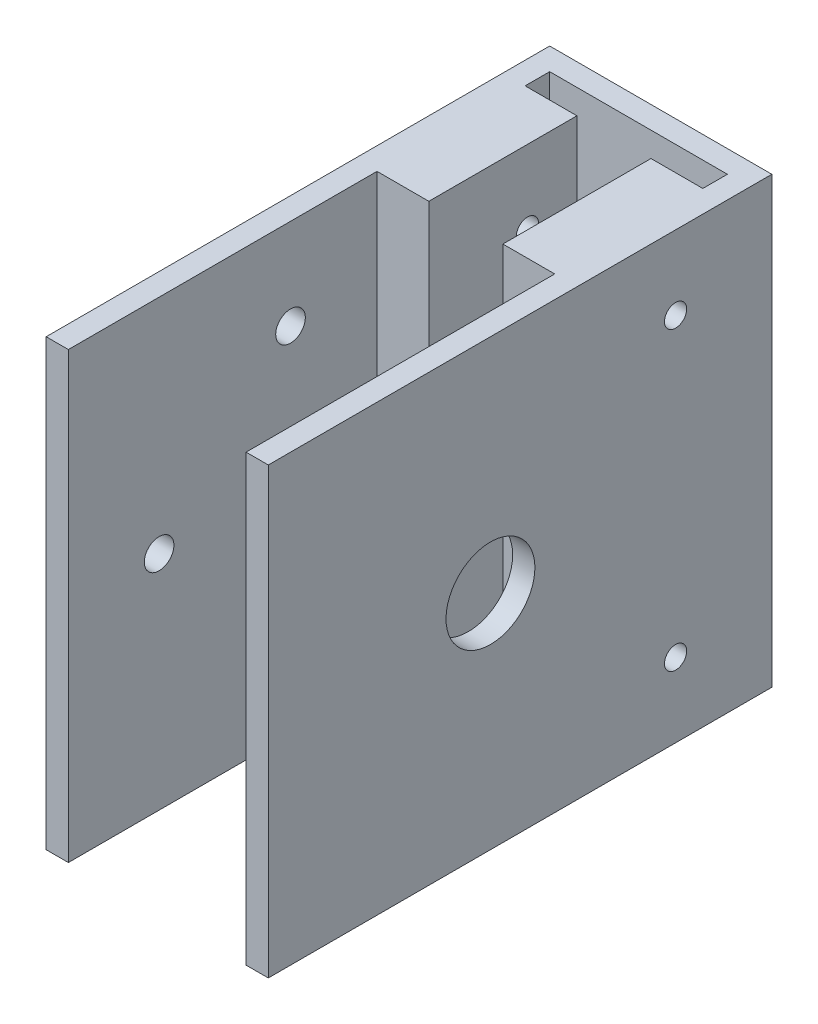
SolidWorks part; units mm, degrees
ref_plane "Front Plane" through (0, 0, 0) normal (0, 0, 1) x (1, 0, 0)
ref_plane "Top Plane" through (0, 0, 0) normal (0, 1, 0) x (1, 0, 0)
ref_plane "Right Plane" through (0, 0, 0) normal (1, 0, 0) x (0, 0, -1)
sketch "Sketch1" plane through (0, 0, 0) normal (0, 0, 1) x (1, 0, 0)
  line L0 (55, 0) -> (-55, 0) construction
  line L1 (-15, 30) -> (15, 30)
  line L2 (-15, 30) -> (-15, -30)
  line L3 (-15, -30) -> (15, -30)
  line L4 (15, 30) -> (15, -30)
  line L5 (-15, 30) -> (15, -30) construction
  line L6 (-15, -30) -> (15, 30) construction
  circle A0 centre (0, 15) radius 2.9
  circle A1 centre (0, -15) radius 2.9
  point P0 (0, 0)
  dimension "D3" = 15
  dimension "D4" = 5.8
  dimension "D1" = 30
  dimension "D2" = 60
extrude "Boss-Extrude1" add sketch "Sketch1" along normal blind 3
sketch "Sketch2" plane through (0, 0, 3) normal (0, 0, 1) x (1, 0, 0)
  line L0 (-15, -30) -> (15, -30) construction
  line L1 (-15, 30) -> (-12, 30)
  line L2 (-15, 30) -> (-15, -30)
  line L3 (-15, -30) -> (-12, -30)
  line L4 (-12, 30) -> (-12, -30)
  line L6 (15, 30) -> (12, 30)
  line L7 (15, 30) -> (15, -30)
  line L8 (15, -30) -> (12, -30)
  line L9 (12, 30) -> (12, -30)
  dimension "D1" = 3
  dimension "D2" = 3
extrude "Boss-Extrude2" add sketch "Sketch2" along normal blind 65
sketch "Sketch5" plane through (0, 30, 0) normal (0, 1, 0) x (1, 0, 0)
  line L0 (12, -68) -> (12, -3) construction
  line L2 (12, -6.3201) -> (5, -6.3201)
  line L3 (12, -6.3201) -> (12, -26.3201)
  line L4 (12, -26.3201) -> (5, -26.3201)
  line L5 (5, -6.3201) -> (5, -26.3201)
  line L6 (0, -33) -> (0, 33) construction
  line L7 (-12, -26.3201) -> (-5, -26.3201)
  line L8 (-12, -6.3201) -> (-5, -6.3201)
  line L9 (-5, -6.3201) -> (-5, -26.3201)
  line M5 (-12, -68) -> (-12, -3)
  line M7 (12, -3) -> (12, -68)
  dimension "D1" = 7
  dimension "D2" = 20
extrude "Boss-Extrude3" add sketch "Sketch5" against normal up to surface (60 mm away) contours L2 L5 L4 M7 | L9 L8 L7 M5 region at (8.5, 30, 16.3201) region at (-8.5, 30, 16.3201) up to face at (0, -30, 34.75)
sketch "Sketch3" plane through (-15, 0, 0) normal (-1, 0, 0) x (0, 0, 1)
  line L0 (68, 30) -> (0, 30) construction
  line L1 (0, 30) -> (0, -30) construction
  line L3 (16.5, 0) -> (-16.5, 0) construction
  circle A0 centre (13, 20) radius 1.5
  circle A1 centre (38, 0) radius 6
  circle A2 centre (20.25, 0) radius 2
  circle A4 centre (38, 17.75) radius 2
  circle A5 centre (55.75, 0) radius 2
  circle A6 centre (38, -17.75) radius 2
  circle A7 centre (13, -20) radius 1.5
  point P20 (38, 0)
  dimension "D1" = 3
  dimension "D2" = 10
  dimension "D3" = 13
  dimension "D4" = 12
  dimension "D5" = 4
  dimension "D6" = 17.75
  dimension "D7" = 38
extrude "Cut-Extrude1" cut sketch "Sketch3" against normal up to next
sketch "Sketch4" plane through (12, 0, 0) normal (-1, 0, 0) x (0, 0, 1)
  circle A0 centre (13, -20) radius 1.5 construction
  circle A1 centre (13, 20) radius 1.5 construction
  circle A2 centre (38, 0) radius 6 construction
  circle A3 centre (13, -20) radius 1.5
  circle A4 centre (13, 20) radius 1.5
  circle A5 centre (38, 0) radius 6
extrude "Cut-Extrude2" cut sketch "Sketch4" against normal through all both and the other way through all
